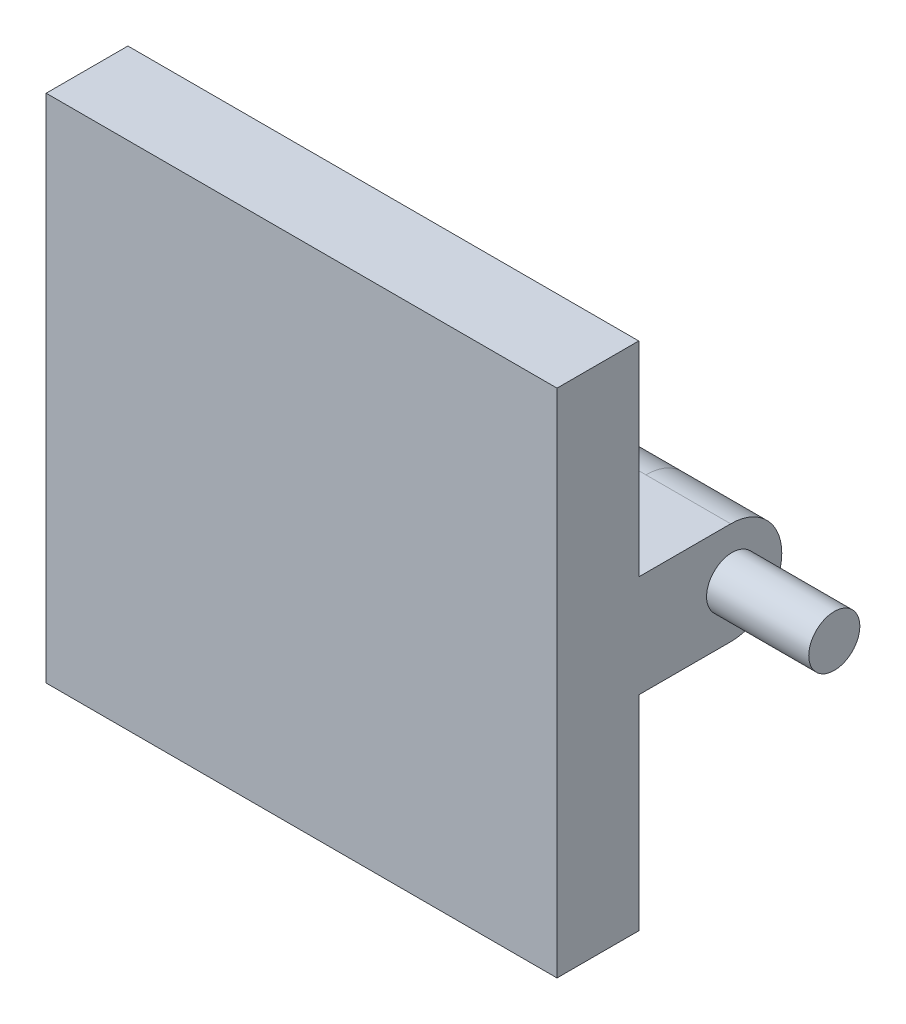
SolidWorks part; units mm, degrees
ref_plane "Front Plane" through (0, 0, 0) normal (0, 0, 1) x (1, 0, 0)
ref_plane "Top Plane" through (0, 0, 0) normal (0, 1, 0) x (1, 0, 0)
ref_plane "Right Plane" through (0, 0, 0) normal (1, 0, 0) x (0, 0, -1)
sketch "Sketch1" plane through (0, 0, 0) normal (0, 0, 1) x (1, 0, 0)
  circle A0 centre (0, 0) radius 12.7
sketch "Sketch9" plane through (0, 0, 0) normal (1, 0, 0) x (0, 0, -1)
  line L0 (0, 0) -> (-25.4, 0) construction
  circle A0 centre (-25.4, 0) radius 6.35
extrude "Boss-Extrude3" add sketch "Sketch1" along normal mid plane 304.8 contours A0
ref_plane "Plane1" through (0, -6.35, 0) normal (0, 1, 0) x (1, 0, 0)
extrude "Boss-Extrude6" add sketch "Sketch9" along normal mid plane 38.1
ref_plane "Plane2" through (0, -6.35, 0) normal (0, 1, 0) x (1, 0, 0)
sketch "Sketch16" plane through (0, -6.35, 0) normal (0, 1, 0) x (1, 0, 0)
  line L0 (0, 0) -> (0, 152.4) construction
  line L1 (12.7, 152.4) -> (-12.7, 152.4) construction
  line L2 (0, 152.4) -> (-12.7, 152.4) construction
  line L3 (12.7, -19.0501) -> (12.7, 152.4) construction
  line L4 (-12.7, 152.4) -> (12.7, 152.4)
  line L5 (-12.7, 152.4) -> (-12.7, 88.9)
  line L6 (-12.7, 88.9) -> (12.7, 88.9)
  line L7 (12.7, 152.4) -> (12.7, 88.9)
extrude "Cut-Extrude2" cut sketch "Sketch16" against normal through all contours L5 L6 L7 L4
ref_plane "Plane3" through (0, 6.35, 0) normal (0, 1, 0) x (1, 0, 0)
sketch "Sketch17" plane through (0, 6.35, 0) normal (0, 1, 0) x (1, 0, 0)
  line L0 (12.7, -19.0501) -> (12.7, 152.4) construction
  line L1 (-12.7, 152.4) -> (12.7, 152.4)
  line L2 (-12.7, 152.4) -> (-12.7, 88.9)
  line L3 (-12.7, 88.9) -> (12.7, 88.9)
  line L4 (12.7, 152.4) -> (12.7, 88.9)
extrude "Cut-Extrude3" cut sketch "Sketch17" along normal through all
sketch "Sketch19" plane through (0, 6.35, 0) normal (0, 1, 0) x (1, 0, 0)
  line L0 (0, 88.9) -> (0, 100.8062) construction
  line L1 (-10.9985, 88.9) -> (10.9985, 88.9) construction
  line L2 (0, 103.3462) -> (0, 132.5562) construction
  line L3 (0, 132.5562) -> (0, 136.525) construction
  line L4 (10.9985, 88.9) -> (-10.9985, 88.9) construction
  line L5 (10.9985, 88.9) -> (-10.9985, 88.9) construction
  circle A0 centre (0, 100.8062) radius 2.54
  circle A1 centre (0, 136.525) radius 2.54
  dimension "D1" = 47.625
  dimension "D2" = 11.9063
extrude "Cut-Extrude5" cut sketch "Sketch19" against normal through all
sketch "Sketch20" plane through (0, -6.35, 0) normal (0, -1, 0) x (1, 0, 0)
  line L0 (0, -88.9) -> (0, -100.8062) construction
  line L1 (-10.9985, -88.9) -> (10.9985, -88.9) construction
  line L2 (0, -88.9) -> (0, -136.525) construction
  circle A0 centre (0, -100.8062) radius 2.54
  circle A1 centre (0, -136.525) radius 2.54
sketch "Sketch21" plane through (0, 0, 152.4) normal (0, 0, 1) x (1, 0, 0)
  line L9 (-10.795, 6.35) -> (10.795, 6.35)
  line L10 (-10.795, 6.35) -> (-10.795, -6.35)
  line L11 (-10.795, -6.35) -> (10.795, -6.35)
  line L12 (10.795, 6.35) -> (10.795, -6.35)
  line L13 (-10.795, 6.35) -> (10.795, -6.35) construction
  line L14 (-10.795, -6.35) -> (10.795, 6.35) construction
  point P0 (0, 0)
extrude "Boss-Extrude8" add sketch "Sketch21" along normal blind 12.7 contours L10 L11 L12 L9
sketch "Sketch25" plane through (-10.795, 0, 0) normal (-1, 0, 0) x (0, 0, 1)
  circle A0 centre (158.75, 0) radius 3.175
sketch "Sketch27" plane through (0, 0, 0) normal (0, 1, 0) x (1, 0, 0)
  line L0 (0, -165.1) -> (0, -165.354) construction
  line L1 (-10.795, -165.1) -> (10.795, -165.1) construction
  line L2 (0, -165.354) -> (11.049, -165.354)
  line L3 (0, -165.354) -> (-11.049, -165.354)
  line L4 (-11.049, -165.354) -> (-11.049, -152.654)
  line L6 (11.049, -165.354) -> (11.049, -152.654)
  line L7 (-11.049, -152.654) -> (-21.209, -152.654)
  line L8 (11.049, -152.654) -> (21.209, -152.654)
  line L9 (-21.209, -152.654) -> (-21.209, -170.434)
  line L10 (-21.209, -170.434) -> (21.209, -170.434)
  line L11 (21.209, -170.434) -> (21.209, -152.654)
extrude "Boss-Extrude9" add sketch "Sketch27" along normal mid plane 12.7 separate body
sketch "Sketch29" plane through (-21.209, 0, 0) normal (-1, 0, 0) x (0, 0, 1)
  circle A0 centre (158.8279, 0) radius 2.921
  point P3 (158.8279, 0)
extrude "Cut-Extrude7" cut sketch "Sketch25" against normal up to next (21.59 mm away)
extrude "Boss-Extrude10" add sketch "Sketch29" against normal blind 35.814
fillet "Fillet2" radius 6.35 4 edges at (16.129, -6.35, 152.654) (16.129, 6.35, 152.654) (-16.129, -6.35, 152.654) (-16.129, 6.35, 152.654)
fillet "Fillet3" radius 6.35 2 edges at (0, -6.35, 165.1) (0, 6.35, 165.1)
sketch "Sketch31" plane through (0, 0, 170.434) normal (0, 0, 1) x (1, 0, 0)
  line L1 (31.75, -31.75) -> (-31.75, -31.75)
  line L2 (31.75, -31.75) -> (31.75, 31.75)
  line L3 (31.75, 31.75) -> (-31.75, 31.75)
  line L4 (-31.75, -31.75) -> (-31.75, 31.75)
  line L5 (31.75, -31.75) -> (-31.75, 31.75) construction
  line L6 (31.75, 31.75) -> (-31.75, -31.75) construction
  point P0 (0, 0)
extrude "Boss-Extrude11" add sketch "Sketch31" along normal blind 10.16
sketch "Sketch32" plane through (0, 31.75, 0) normal (0, 1, 0) x (1, 0, 0)
  line L1 (-43.9507, 155.0176) -> (83.0493, 155.0176)
  line L2 (-43.9507, 155.0176) -> (-43.9507, -152.4)
  line L3 (-43.9507, -152.4) -> (83.0493, -152.4)
  line L4 (83.0493, 155.0176) -> (83.0493, -152.4)
extrude "Cut-Extrude8" cut sketch "Sketch32" against normal through all
sketch "Sketch33" plane through (0, 31.75, 0) normal (0, 1, 0) x (1, 0, 0)
  line L1 (-10.795, -152.4) -> (10.795, -152.4)
  line L2 (-10.795, -152.4) -> (-10.795, -165.1)
  line L3 (-10.795, -165.1) -> (10.795, -165.1)
  line L4 (10.795, -152.4) -> (10.795, -165.1)
extrude "Cut-Extrude9" cut sketch "Sketch33" against normal through all
extrude "Boss-Extrude12" add sketch "Sketch29<2>" against normal blind 35.814 contours A0
sketch "Sketch29<2>" plane through (-21.209, 0, 0) normal (-1, 0, 0) x (0, 0, 1) same geometry as "Sketch29"
sketch "Sketch37" plane through (21.209, 0, 0) normal (1, 0, 0) x (0, 0, -1)
  line L0 (-170.434, 6.35) -> (-152.654, 6.35)
  line L1 (-152.654, 6.35) -> (-152.654, -6.35)
  line L2 (-170.434, -6.35) -> (-152.654, -6.35)
  line L3 (-170.434, -6.35) -> (-170.434, 6.35)
extrude "Boss-Extrude13" add sketch "Sketch37" along normal blind 10.541
fillet "Fillet5" radius 6.35 2 edges at (26.4795, -6.35, 152.654) (26.4795, 6.35, 152.654)
sketch "Sketch38" plane through (31.75, 0, 0) normal (1, 0, 0) x (0, 0, -1)
  circle A1 centre (-158.8279, 0) radius 3.175
extrude "Boss-Extrude14" add sketch "Sketch38" along normal blind 12.7
